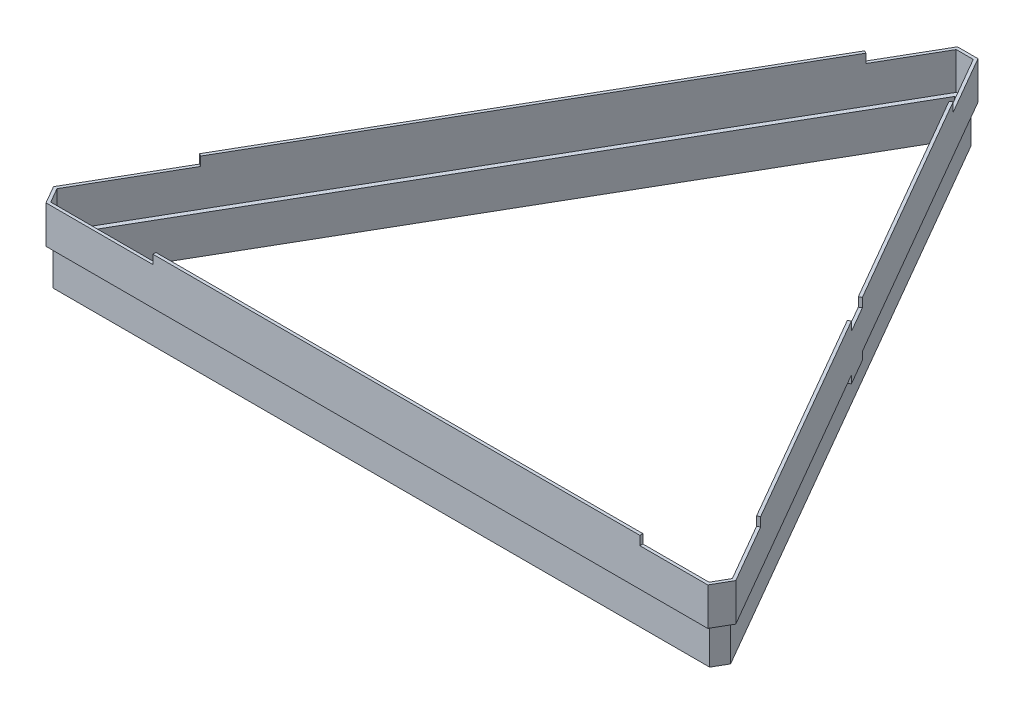
SolidWorks part; units mm, degrees
ref_plane "Front Plane" through (0, 0, 0) normal (0, 0, 1) x (1, 0, 0)
ref_plane "Top Plane" through (0, 0, 0) normal (0, 1, 0) x (1, 0, 0)
ref_plane "Right Plane" through (0, 0, 0) normal (1, 0, 0) x (0, 0, -1)
sketch "Sketch1" plane through (0, 0, 0) normal (0, 1, 0) x (1, 0, 0)
  line L17 (-4, 192.2576) -> (111, -6.9282) construction
  line L24 (4, 192.2576) -> (-111, -6.9282) construction
  line L25 (-115, 0) -> (115, 0) construction
  line L26 (-96.004, 30.9021) -> (-95.1379, 30.4021)
  line L27 (-111.2679, -2.4641) -> (-110.8349, -2.2141) construction
  line L28 (0, 192.2576) -> (0, 185.3294) construction
  line L29 (113, -3.4641) -> (107, 0) construction
  line L30 (59.5, 96.1288) -> (57.7679, 95.1288) construction
  line L31 (-59.5, 96.1288) -> (-57.7679, 95.1288) construction
  line L33 (-112.6906, 0) -> (-109.8453, -4.9282)
  line L36 (112.6906, 0) -> (109.8453, -4.9282)
  line L37 (-2.8453, 190.2576) -> (2.8453, 190.2576)
  line L46 (-74.74, -4.9282) -> (87.75, -4.9282)
  line L50 (-112.6906, 0) -> (-95.1379, 30.4021)
  line L51 (-13.8929, 171.1225) -> (-95.1379, 30.4021)
  line L52 (-14.759, 171.6225) -> (-13.8929, 171.1225)
  line L53 (-14.759, 171.6225) -> (-96.004, 30.9021)
  line L54 (13.8929, 171.1225) -> (14.759, 171.6225)
  line L55 (-109.8453, -4.9282) -> (-74.74, -4.9282)
  line L56 (109.8453, -4.9282) -> (87.75, -4.9282)
  line L57 (-74.74, -5.9282) -> (-74.74, -4.9282)
  line L58 (61.134, 91.2987) -> (56.134, 99.9589)
  line L59 (-2.8453, 190.2576) -> (-13.8929, 171.1225)
  line L60 (61.134, 91.2987) -> (102.509, 19.6351)
  line L61 (102.509, 19.6351) -> (113.8453, 0)
  line L62 (101.6429, 19.1351) -> (102.509, 19.6351)
  line L63 (101.6429, 19.1351) -> (112.6906, 0)
  line L64 (2.8453, 190.2576) -> (13.8929, 171.1225)
  line L65 (113.8453, 0) -> (110.4226, -5.9282)
  line L66 (56.134, 99.9589) -> (14.759, 171.6225)
  line L67 (55.2679, 99.4589) -> (13.8929, 171.1225)
  line L68 (0, -6.9282) -> (-74.74, -6.9282) construction
  line L69 (-14.759, 171.6225) -> (-3.4226, 191.2576)
  line L70 (-58.634, 95.6288) -> (-96.004, 30.9021) construction
  line L71 (-3.4226, 191.2576) -> (3.4226, 191.2576)
  line L72 (60.2679, 90.7987) -> (61.134, 91.2987)
  line L73 (55.2679, 99.4589) -> (56.134, 99.9589)
  line L74 (55.2679, 99.4589) -> (60.2679, 90.7987)
  line L75 (-74.74, -5.9282) -> (87.75, -5.9282)
  line L76 (60.2679, 90.7987) -> (101.6429, 19.1351)
  line L77 (57.7679, 95.1288) -> (57.3349, 94.8788) construction
  line L78 (57.3349, 94.8788) -> (-110.8349, -2.2141) construction
  line L79 (-110.8349, -2.2141) -> (-112.1132, 0)
  line L80 (-112.1132, 0) -> (-2.5566, 189.7576)
  line L81 (-2.5566, 189.7576) -> (2.5566, 189.7576)
  line L82 (2.5566, 189.7576) -> (112.1132, 0)
  line L83 (112.1132, 0) -> (109.5566, -4.4282)
  line L84 (109.5566, -4.4282) -> (-109.5566, -4.4282)
  line L85 (-109.5566, -4.4282) -> (-110.8349, -2.2141)
  line L86 (-57.3349, 94.8788) -> (-56.4689, 94.3788) construction
  line L93 (-56.4689, 94.3788) -> (-1.9793, 188.7576)
  line L94 (-1.9793, 188.7576) -> (1.9793, 188.7576)
  line L95 (1.9793, 188.7576) -> (110.9585, 0)
  line L96 (110.9585, 0) -> (108.9793, -3.4282)
  line L97 (108.9793, -3.4282) -> (-108.9793, -3.4282)
  line L98 (-108.9793, -3.4282) -> (-110.9585, 0)
  line L99 (-110.9585, 0) -> (-56.4689, 94.3788)
  line L100 (-111.2679, -2.4641) -> (-112.134, -2.9641) construction
  line L101 (-112.134, -2.9641) -> (-113.8453, 0)
  line L102 (-113.8453, 0) -> (-96.004, 30.9021)
  line L103 (-112.134, -2.9641) -> (-110.4226, -5.9282)
  line L104 (-110.4226, -5.9282) -> (-74.74, -5.9282)
  line L105 (3.4226, 191.2576) -> (14.759, 171.6225)
  line L106 (110.4226, -5.9282) -> (87.75, -5.9282)
  line L107 (87.75, -5.9282) -> (87.75, -4.9282)
  point P23 (-57.7679, 95.1288)
  point P28 (57.7679, 95.1288)
  point P29 (58.634, 95.6288)
  point P34 (-58.634, 95.6288)
  point P38 (14.759, 171.6225)
  point P41 (-14.759, 171.6225)
  point P44 (102.509, 19.6351)
  point P47 (-96.004, 30.9021)
  point P48 (59.5, 96.1288)
  point P62 (-54.7369, 93.3788)
  dimension "D1" = 8
  dimension "D2" = 8
  dimension "D3" = 8
  dimension "D4" = 230
  dimension "D5" = 230
  dimension "D6" = 230
  dimension "D7" = 74.74
  dimension "D8" = 2
extrude "Boss-Extrude1" add sketch "Sketch1" along normal blind 0.2 contours L59 L37 L64 | L76 L74 L67 L64 L37 L59 L51 L50 L33 L55 L46 L56 L36 L63 L84 L85 L79 L80 L81 L82 L83 | L67 | L74 | L76 | L63 L36 L56 | L46 | L55 L33 L50 | L51 | L85 L84 L83 L82 L81 L80 L79 region at (-54.9485, 0, -101.0123) region at (-95.8396, 0, -30.1869) region at (-54.2572, 0, -100.6132) region at (-8.7814, 0, -181.2614) region at (6.505, 0, 5.4282) region at (35.0135, 0, -135.5407) region at (98.7976, 0, 5.2935) region at (58.201, 0, -95.3788) region at (81.3885, 0, -55.2169) region at (-111.2172, 0, 0.9587)
extrude "Boss-Extrude2" add sketch "Sketch1<7>" along normal blind 12.58 contours L63 L36 L56 | L59 L37 L64 | L55 L33 L50 | L74 region at (-95.8396, 0, -30.1869) region at (-8.7814, 0, -181.2614) region at (98.7976, 0, 5.2935) region at (58.201, 0, -95.3788)
sketch "Sketch1<7>" plane through (0, 0, 0) normal (0, 1, 0) x (1, 0, 0) same geometry as "Sketch1"
extrude "Boss-Extrude3" add sketch "Sketch1<8>" along normal blind 15.58 contours L46 | L51 | L76 | L67 region at (-54.9485, 0, -101.0123) region at (6.505, 0, 5.4282) region at (35.0135, 0, -135.5407) region at (81.3885, 0, -55.2169)
sketch "Sketch1<8>" plane through (0, 0, 0) normal (0, 1, 0) x (1, 0, 0) same geometry as "Sketch1"
extrude "Boss-Extrude4" add sketch "Sketch1<9>" against normal blind 12.38 contours L85 L84 L83 L82 L81 L80 L79 region at (-111.2172, 0, 0.9587)
sketch "Sketch1<9>" plane through (0, 0, 0) normal (0, 1, 0) x (1, 0, 0) same geometry as "Sketch1"
extrude "Boss-Extrude5" add sketch "Sketch1<10>" against normal blind 2.58 contours L74 region at (58.201, 0, -95.3788)
sketch "Sketch1<10>" plane through (0, 0, 0) normal (0, 1, 0) x (1, 0, 0) same geometry as "Sketch1"
